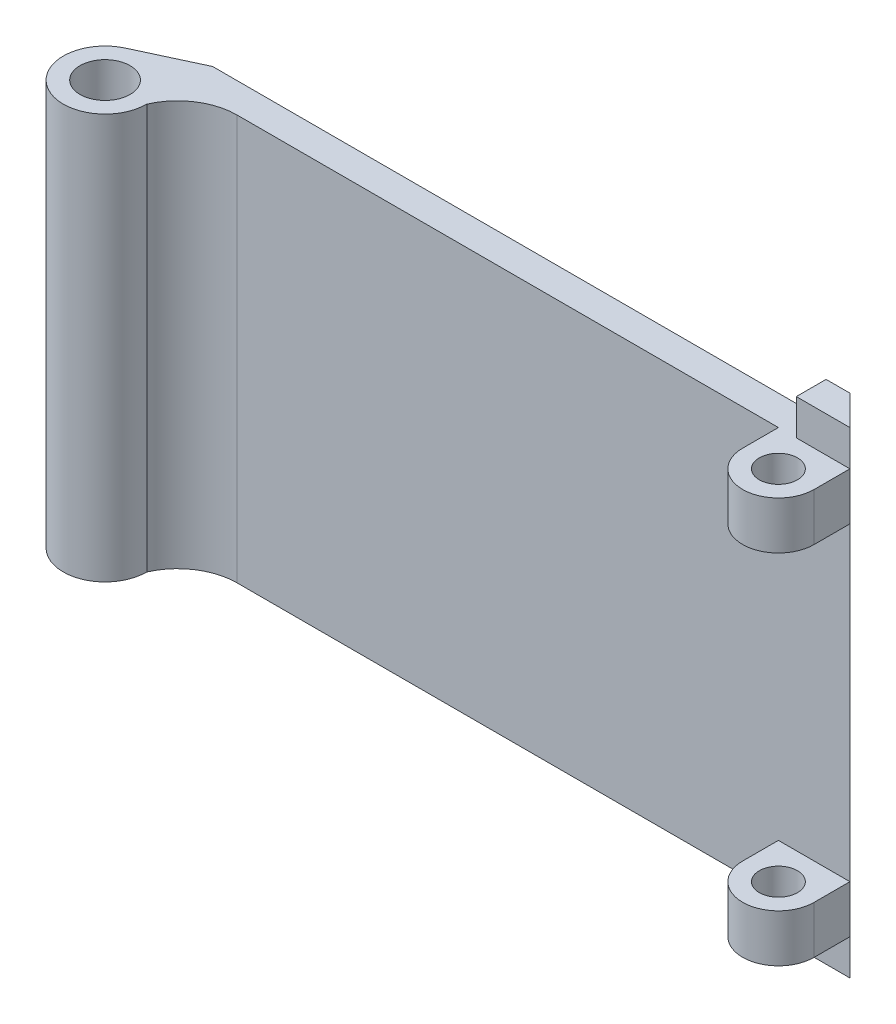
SolidWorks part; units mm, degrees
ref_plane "前视基准面" through (0, 0, 0) normal (0, 0, 1) x (1, 0, 0)
ref_plane "上视基准面" through (0, 0, 0) normal (0, 1, 0) x (1, 0, 0)
ref_plane "右视基准面" through (0, 0, 0) normal (1, 0, 0) x (0, 0, -1)
other "Configuration Table"
sketch "草图1" plane through (0, 0, 0) normal (0, 0, 1) x (1, 0, 0)
  line L0 (0, 0) -> (0, 34)
  line L1 (0, 0) -> (60, 0)
  line L2 (0, 34) -> (60, 34)
  line L3 (60, 0) -> (60, 34)
  dimension "D1" = 34
  dimension "D2" = 60
extrude "凸台-拉伸1" add sketch "草图1" along normal blind 2.5
sketch "草图3" plane through (0, 0, 0) normal (0, -1, 0) x (1, 0, 0)
  line L0 (0, 2.5) -> (60, 2.5) construction
  line L1 (0, 2.5) -> (0, 0) construction
  line L2 (0, 5.5) -> (0, 2.5)
  line L3 (6, 5.5) -> (6, 2.5)
  circle A0 centre (3, 5.5) radius 1.6
  circle A1 centre (3, 5.5) radius 3
  line M5 (60, 2.5) -> (0, 2.5)
  dimension "D1" = 3.2
  dimension "D2" = 3
  dimension "D3" = 3
  dimension "D4" = 6
extrude "凸台-拉伸2" add sketch "草图3" against normal blind 4 contours A1 L3 M5 | A1 L2 M5 | A1 A0 region at (0.6701, 0, 3.1701) region at (3, 0, 8.4151) region at (5.3299, 0, 3.1701)
pattern_linear "阵列(线性)1" count 2 spacing 56.5 along (1, 0, 0) count 2 spacing 30 along (0, 1, 0) of "凸台-拉伸2"
sketch "草图5" plane through (0, 0, 0) normal (-1, 0, 0) x (0, 0, 1)
  line L0 (5.5, 0) -> (0, 0) construction
  line L1 (0, 34) -> (2.5, 34)
  line L2 (0, 34) -> (0, 0)
  line L3 (0, 0) -> (2.5, 0)
  line L4 (2.5, 34) -> (2.5, 0)
  line L5 (2.5, 30) -> (2.5, 4) construction
extrude "凸台-拉伸3" add sketch "草图5" along normal blind 4
sketch "草图6" plane through (60, 0, 0) normal (1, 0, 0) x (0, 0, -1)
  line L1 (0, 34) -> (-2.5, 34)
  line L2 (0, 34) -> (0, 0)
  line L3 (0, 0) -> (-2.5, 0)
  line L4 (-2.5, 34) -> (-2.5, 0)
extrude "凸台-拉伸4" add sketch "草图6" along normal blind 4
sketch "草图7" plane through (0, 34, 0) normal (0, 1, 0) x (1, 0, 0)
  line L0 (3, -2.5) -> (3, 0)
  line L1 (64, 0) -> (-4, 0) construction
  circle A0 centre (3, -5.5) radius 3
  line M2 (64, 0) -> (-4, 0)
  line M3 (-4, 0) -> (-4, -2.5)
  line M4 (-4, -2.5) -> (0, -2.5)
  line M5 (0, -2.5) -> (0, -5.5)
  dimension "D1" = 6
extrude "切除-拉伸1" cut sketch "草图7" against normal through all contours A0 L0 M2 M3 M4 M5 region at (-0.3837, 34, 1.4409)
sketch "草图8" plane through (0, 4, 0) normal (0, 1, 0) x (1, 0, 0)
  circle A0 centre (3, -5.5) radius 1.6
  circle A1 centre (3, -5.5) radius 3
  circle M1 centre (3, -5.5) radius 1.6
  line M2 (6, -2.5) -> (3, -2.5)
  arc M3 (3, -2.5) -> (6, -5.5) centre (3, -5.5) ccw
  line M4 (6, -5.5) -> (6, -2.5)
extrude "凸台-拉伸13" add sketch "草图8" along normal up to surface (26 mm away) contours A1 M3 M1 | A1 M4 M2 region at (0.9387, 4, 7.5613) region at (5.3299, 4, 3.1701)
sketch "草图9" plane through (0, 34, 0) normal (0, 1, 0) x (1, 0, 0)
  line L0 (1.5, -2.9019) -> (6.5263, 0)
  line L1 (1.5, -2.9019) -> (6, -2.9019) construction
  line L2 (64, 0) -> (3, 0) construction
  line L3 (6, -5.5) -> (6, -2.5) construction
  line L4 (6, -3.1906) -> (7.1962, -2.5)
  line L5 (56.5, -2.5) -> (6, -2.5) construction
  arc A1 (3, -2.5) -> (6, -5.5) centre (3, -5.5) ccw construction
  line M6 (3, 0) -> (3, -2.5)
  arc M7 (3, -2.5) -> (6, -5.5) centre (3, -5.5) ccw
  line M8 (6, -5.5) -> (6, -2.5)
  line M9 (6, -2.5) -> (56.5, -2.5)
  line M15 (64, 0) -> (3, 0)
  dimension "D1" = 30
  dimension "D2" = 2.5
extrude "切除-拉伸2" cut sketch "草图9" against normal through all contours L0 M6 M15 region at (4.1754, 34, 0.6786)
extrude "凸台-拉伸14" add sketch "草图9<3>" against normal up to surface (34 mm away) contours L4 M8 M9 | L0 M7 M6 region at (2.6144, 34, 2.3993) region at (6.3987, 34, 2.7302) up to face at (61.1, 0, 5.5)
sketch "草图9<3>" plane through (0, 34, 0) normal (0, 1, 0) x (1, 0, 0) same geometry as "草图9"
sketch "草图10" plane through (0, 34, 0) normal (0, 1, 0) x (1, 0, 0)
  line L0 (64, -2.5) -> (62.5, -2.5)
  line L1 (64, -2.5) -> (64, 0)
  line L2 (62.5, -2.5) -> (62.5, 0)
  line L3 (64, 0) -> (62.5, 0)
  line L4 (64, -2.5) -> (62.5, -2.5) construction
  dimension "D1" = 1.5
extrude "切除-拉伸3" cut sketch "草图10" against normal up to surface (34 mm away) up to face at (35.5429, 0, 3.59)
sketch "草图11" plane through (0, 34, 0) normal (0, 1, 0) x (1, 0, 0)
  line L0 (62.5, -2.5) -> (60, 0)
  line L1 (62.5, 0) -> (6.5263, 0) construction
  line L3 (56.5, -2.5) -> (62.5, -2.5) construction
  line L4 (56.5, -2.5) -> (62.5, -2.5)
  point P5 (62.5, -2.75)
  point P6 (0, 0)
  point P10 (62.5, -2.75)
  line M2 (7.1962, -2.5) -> (56.5, -2.5)
  line M3 (62.5, -5.5) -> (62.5, 0)
  line M4 (62.5, 0) -> (6.5263, 0)
  dimension "D1" = 45
extrude "切除-拉伸4" cut sketch "草图11" against normal through all and the other way through all contours L0 M2 M3 M4 region at (61.6667, 34, 0.8333)
sketch "草图13" plane through (0, 34, 0) normal (0, 1, 0) x (1, 0, 0)
  line L0 (62.5, -2.5) -> (58, -2.5)
  line L1 (58, -2.5) -> (58, 0)
  line L2 (60, 0) -> (6.5263, 0) construction
  line L3 (58, 0) -> (60, 0)
  line L4 (60, 0) -> (62.5, -2.5)
  dimension "D2" = 2
extrude "凸台-拉伸16" add sketch "草图13" along normal blind 3 contours L0 L1 L3 L4
sketch "草图14" plane through (0, 0, 0) normal (0, -1, 0) x (1, 0, 0)
  line L0 (62.5, 2.5) -> (60, 0)
  line L1 (60, 0) -> (58, 0)
  line L2 (6.5263, 0) -> (60, 0) construction
  line L3 (58, 0) -> (58, 2.5)
  line L4 (58, 2.5) -> (62.5, 2.5)
  dimension "D1" = 2
extrude "凸台-拉伸17" add sketch "草图14" along normal blind 3
sketch "草图15" plane through (0, 0, 0) normal (0, -1, 0) x (1, 0, 0)
  circle A0 centre (3, 5.5) radius 2.1
  dimension "D1" = 4.2
extrude "切除-拉伸6" cut sketch "草图15" against normal through all
sketch "草图16" plane through (0, 0, 0) normal (0, -1, 0) x (-1, 0, 0)
  line L0 (-6.5, -5.5) -> (-7.1962, -2.5)
  line L1 (-1.524, -2.3264) -> (-6.5263, 0)
  circle A0 centre (-3, -5.5) radius 3.5
  circle A1 centre (-3, -5.5) radius 2.1
  line M11 (-7.1962, -2.5) -> (-6, -3.1906)
  line M12 (-6, -3.1906) -> (-6, -5.5)
  arc M13 (-6, -5.5) -> (-1.5, -2.9019) centre (-3, -5.5) ccw
  line M14 (-1.5, -2.9019) -> (-6.5263, 0)
  dimension "D1" = 7
  dimension "D2" = 4.2
extrude "凸台-拉伸18" add sketch "草图16" against normal up to surface (34 mm away) contours A0 M14 M13 M12 M11 | A0 L0 M11 | A0 L1 M14 region at (6.2773, 0, 4.591) region at (6.5601, 0, 3.6739) region at (3.8552, 0, 1.3691) up to face at (5.1, 34, 5.5)
fillet "圆角1" radius 5 1 edges at (7.1962, 17, 2.5)
